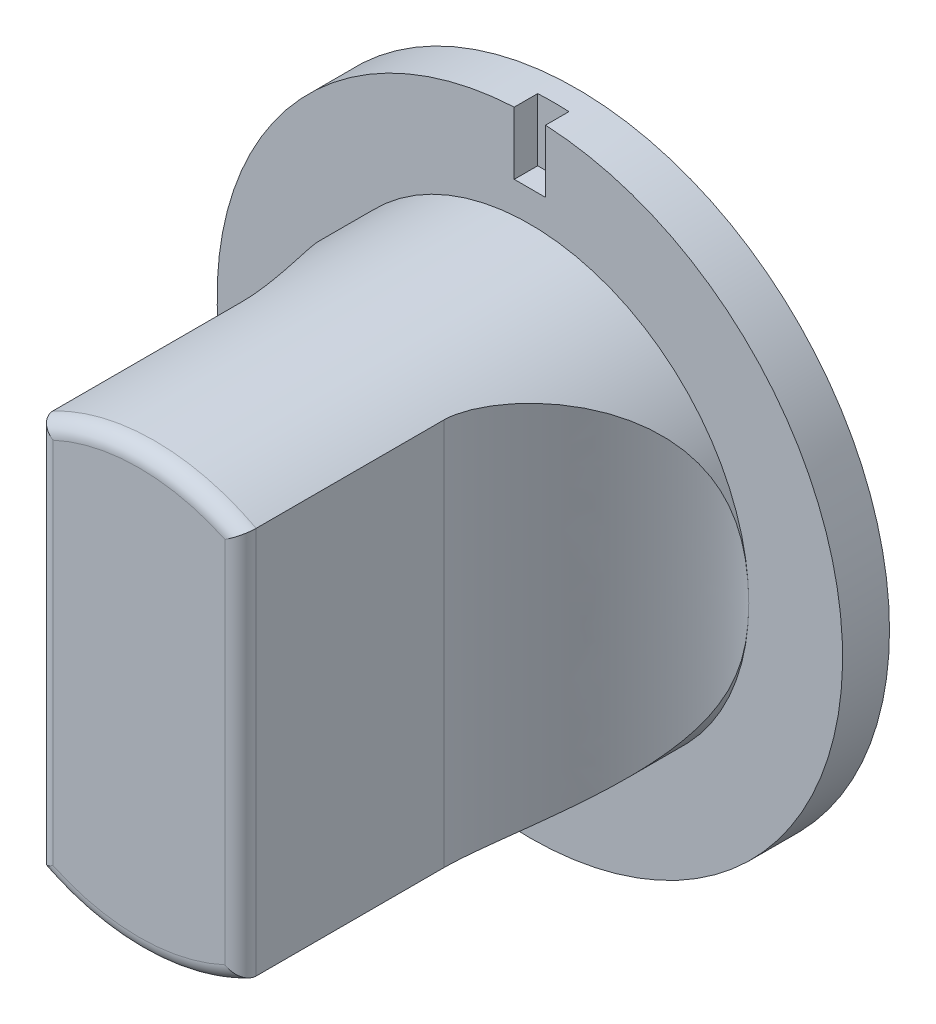
SolidWorks part; units mm, degrees
ref_plane "Front Plane" through (0, 0, 0) normal (0, 0, 1) x (1, 0, 0)
ref_plane "Top Plane" through (0, 0, 0) normal (0, 1, 0) x (1, 0, 0)
ref_plane "Right Plane" through (0, 0, 0) normal (1, 0, 0) x (0, 0, -1)
sketch "Sketch1" plane through (0, 0, 0) normal (0, 0, 1) x (1, 0, 0)
  circle A0 centre (0, 0) radius 10
  dimension "D1" = 20
extrude "Boss-Extrude1" add sketch "Sketch1" along normal blind 1.5
sketch "Sketch2" plane through (0, 0, 1.5) normal (0, 0, 1) x (1, 0, 0)
  line L0 (0, 7) -> (0, -7) construction
  line L1 (-3.25, 6.1998) -> (-3.25, -6.1998)
  line L2 (3.25, 6.1998) -> (3.25, -6.1998)
  arc A0 (-3.25, -6.1998) -> (3.25, -6.1998) centre (0, 0) ccw
  arc A1 (3.25, 6.1998) -> (-3.25, 6.1998) centre (0, 0) ccw
  point P7 (-3.5998, -7.1443)
  dimension "D1" = 14
  dimension "D2" = 3.25
extrude "Boss-Extrude2" add sketch "Sketch2" along normal blind 12.5
sketch "Sketch4" plane through (0, 0, 1.5) normal (0, 0, 1) x (1, 0, 0)
  line L0 (-0.5, 9.9875) -> (-0.5, 7.9875)
  line L1 (-0.5, 7.9875) -> (0.5, 7.9875)
  line L2 (0.5, 7.9875) -> (0.5, 9.9875)
  arc A0 (0.5, 9.9875) -> (-0.5, 9.9875) centre (0, 0) ccw
  dimension "D4" = 20
  dimension "D1" = 0.5
  dimension "D2" = 0.5
  dimension "D3" = 2
extrude "Cut-Extrude2" cut sketch "Sketch4" against normal blind 0.75
sketch "Sketch5" plane through (0, 0, 0) normal (0, 0, -1) x (-1, 0, 0)
  circle A0 centre (0, 0) radius 3.1
  dimension "D1" = 6.2
extrude "Cut-Extrude3" cut sketch "Sketch5" against normal blind 7
fillet "Fillet5" radius 3.75 2 edges at (3.25, 0, 1.5) (-3.25, 0, 1.5) second distance 6 conic rho 0.25 first distance on face at (0, 3.9906, 1.5)
fillet "Fillet6" radius 0.5 4 edges at (3.25, 0, 14) (0, -7, 14) (-3.25, 0, 14) (0, 7, 14)
